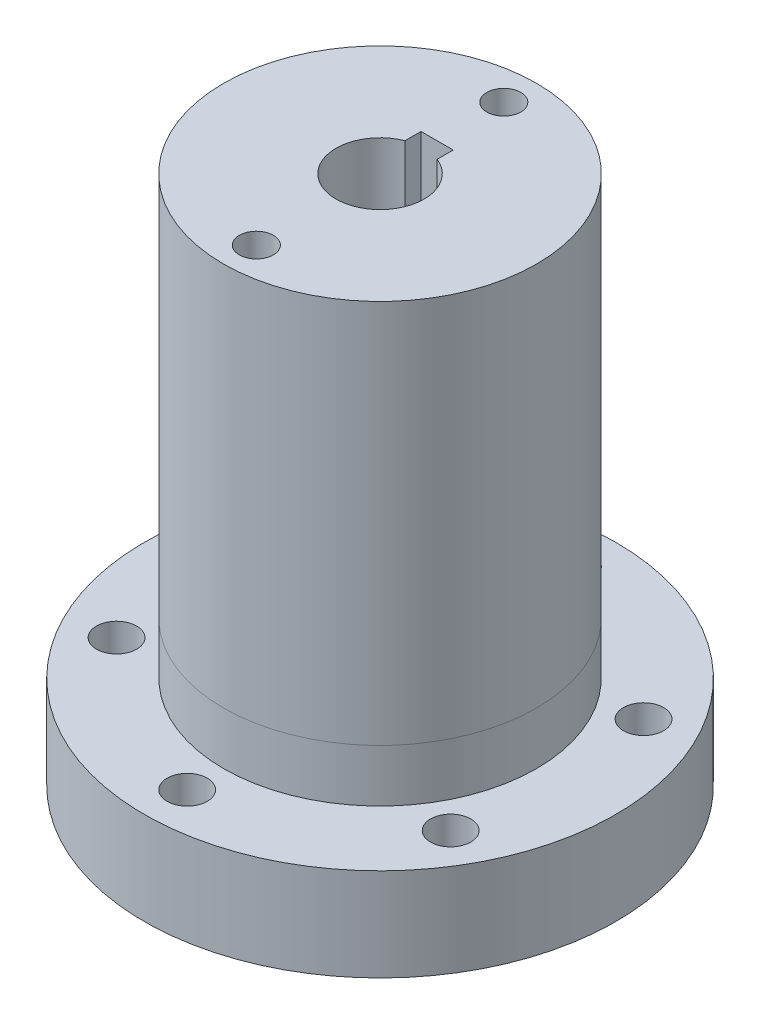
SolidWorks part; units mm, degrees
ref_plane "Front Plane" through (0, 0, 0) normal (0, 0, 1) x (1, 0, 0)
ref_plane "Top Plane" through (0, 0, 0) normal (0, 1, 0) x (1, 0, 0)
ref_plane "Right Plane" through (0, 0, 0) normal (1, 0, 0) x (0, 0, -1)
sketch "Sketch1" plane through (0, 0, 0) normal (0, 1, 0) x (1, 0, 0)
  circle A0 centre (0, 0) radius 25.28
extrude "Boss-Extrude1" add sketch "Sketch1" along normal blind 8.5
sketch "Sketch2" plane through (0, 8.5, 0) normal (0, 1, 0) x (1, 0, 0)
  circle A0 centre (0, 0) radius 25.3
extrude "Boss-Extrude2" add sketch "Sketch2" along normal blind 57.15
sketch "Sketch7" plane through (0, 65.65, 0) normal (0, 1, 0) x (1, 0, 0)
  circle A0 centre (0, 0) radius 25.3
extrude "Boss-Extrude4" add sketch "Sketch7" along normal blind 15
sketch "Sketch5" plane through (0, 0, 0) normal (0, -1, 0) x (1, 0, 0)
  line L1 (-2.575, 9.15) -> (2.575, 9.15)
  line L2 (-2.575, 9.15) -> (-2.575, 4)
  line L3 (-2.575, 4) -> (2.575, 4)
  line L4 (2.575, 9.15) -> (2.575, 4)
  circle A0 centre (0, 0) radius 7.25
  dimension "D1" = 5.15
  dimension "D2" = 5.15
  dimension "D3" = 9.15
  dimension "D4" = 2.575
extrude "Cut-Extrude3" cut sketch "Sketch5" against normal blind 115 contours L2 A0 L4 L3 | L4 A0 L2 L3 | A0 L4 L1 L2 region at (0, 0, 8.1175) region at (0, 0, 5.5505) region at (0, 0, -0.5929)
sketch "Sketch6" plane through (0, 0, 0) normal (0, -1, 0) x (1, 0, 0)
  circle A0 centre (0, 0) radius 38.1
extrude "Boss-Extrude3" add sketch "Sketch6" along normal blind 15
sketch "Sketch9" plane through (0, 0, 0) normal (0, 1, 0) x (1, 0, 0)
  line L1 (0, 31.1769) -> (-27, 15.5885)
  line L2 (-27, 15.5885) -> (-27, -15.5885)
  line L3 (-27, -15.5885) -> (0, -31.1769)
  line L4 (0, -31.1769) -> (27, -15.5885)
  line L5 (27, -15.5885) -> (27, 15.5885)
  line L6 (27, 15.5885) -> (0, 31.1769)
  circle A0 centre (0, 0) radius 27 construction
  circle A1 centre (0, 31.1769) radius 3.25
  circle A2 centre (-27, 15.5885) radius 3.25
  circle A3 centre (-27, -15.5885) radius 3.25
  circle A4 centre (0, -31.1769) radius 3.25
  circle A5 centre (27, -15.5885) radius 3.25
  circle A6 centre (27, 15.5885) radius 3.25
extrude "Cut-Extrude4" cut sketch "Sketch9" against normal blind 20 contours L1 A2 L2 | L2 A2 L1 | L6 A1 L1 | L1 A1 L6 | L5 A6 L6 | L6 A6 L5 | L4 A5 L5 | L5 A5 L4 | L3 A4 L4 | L4 A4 L3 | L2 A3 L3 | L3 A3 L2 region at (0, 0, -29.3851) region at (0, 0, -32.0728) region at (-25.4482, 0, -14.6925) region at (-27.7759, 0, -16.0364) region at (27.7759, 0, -16.0364) region at (25.4482, 0, -14.6925) region at (-25.4482, 0, 14.6925) region at (-27.7759, 0, 16.0364) region at (27.7759, 0, 16.0364) region at (25.4482, 0, 14.6925) region at (0, 0, 29.3851) region at (0, 0, 32.0728)
sketch "Sketch10" plane through (0, 80.65, 0) normal (0, 1, 0) x (1, 0, 0)
  circle A0 centre (0, 20) radius 2.75
  circle A1 centre (0, -20) radius 2.75
  arc A2 (2.575, -6.7773) -> (-2.575, -6.7773) centre (0, 0) ccw construction
  dimension "D1" = 20
  dimension "D2" = 20
extrude "Cut-Extrude6" cut sketch "Sketch10" against normal blind 129
sketch "Sketch11" plane through (0, 80.65, 0) normal (0, 1, 0) x (1, 0, 0)
  line L1 (-2.575, -9.15) -> (2.575, -9.15)
  line L3 (0, -7.12) -> (0, -9.15)
  circle A0 centre (0, 0) radius 7.12
  arc M3 (-2.575, -6.7773) -> (2.575, -6.7773) centre (0, 0) cw
  line M4 (2.575, -6.7773) -> (2.575, -9.15)
  line M5 (2.575, -9.15) -> (-2.575, -9.15)
  line M6 (-2.575, -9.15) -> (-2.575, -6.7773)
  dimension "D1" = 14.24
extrude "Boss-Extrude5" add sketch "Sketch11" against normal blind 93 contours A0 M3 | A0 M6 M5 M4 region at (0, 80.65, 0) region at (-2.3561, 80.65, 7.9637)
sketch "Sketch12" plane through (0, 80.65, 0) normal (0, 1, 0) x (1, 0, 0)
  circle A0 centre (0, 0) radius 25.3
extrude "Cut-Extrude8" cut sketch "Sketch12" against normal blind 10
sketch "Sketch13" plane through (0, 70.65, 0) normal (0, 1, 0) x (1, 0, 0)
  line L0 (0, 7.12) -> (0, 9.22)
  line L1 (0, 9.22) -> (2.6, 9.22)
  line L2 (0, 9.22) -> (-2.6, 9.22)
  line L3 (-2.6, 9.22) -> (-2.6, 6.6283)
  line L4 (2.6, 9.22) -> (2.6, 6.6283)
  circle A0 centre (0, 0) radius 7.12
extrude "Cut-Extrude9" cut sketch "Sketch13" against normal blind 30 contours A0 | A0 L0 L2 L3 | A0 L4 L1 L0 region at (-1.3468, 70.65, -8.0845) region at (1.3468, 70.65, -8.0845) region at (0, 70.65, 0)
